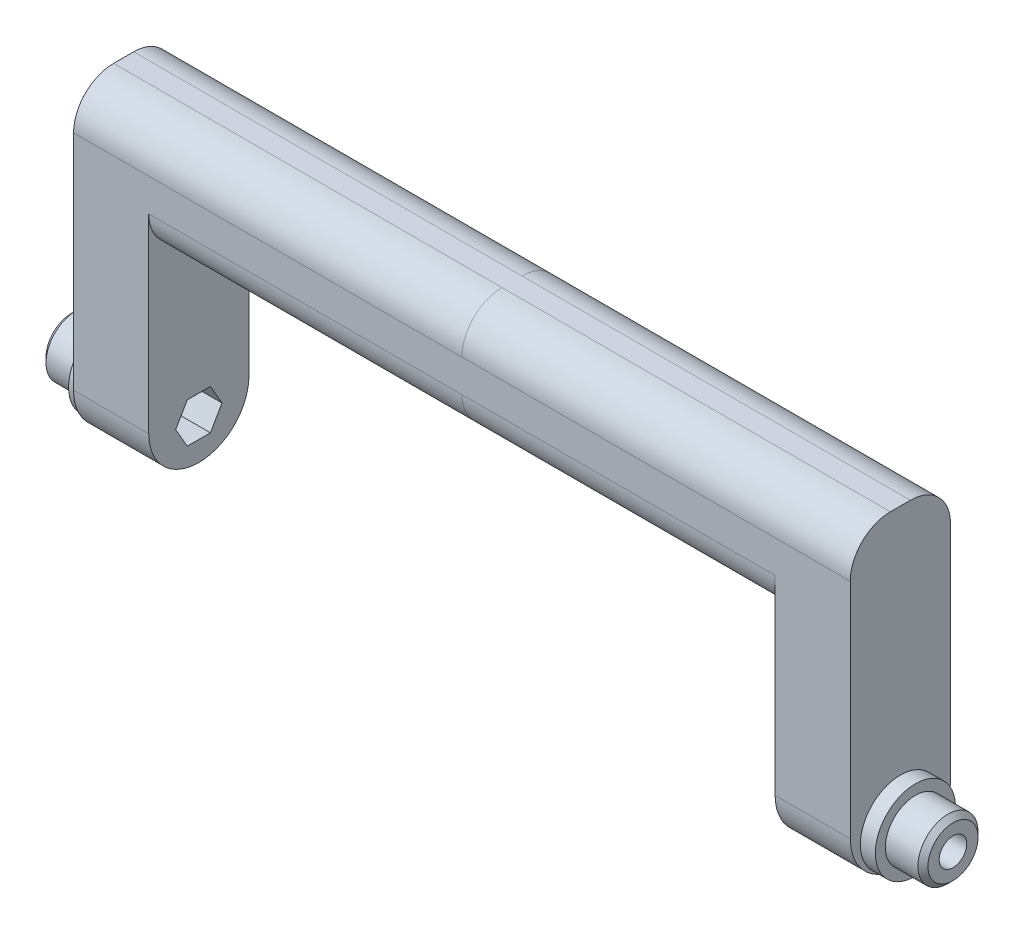
SolidWorks part; units mm, degrees
material "PET"
ref_plane "Front Plane" through (0, 0, 0) normal (0, 0, 1) x (1, 0, 0)
ref_plane "Top Plane" through (0, 0, 0) normal (0, 1, 0) x (1, 0, 0)
ref_plane "Right Plane" through (0, 0, 0) normal (1, 0, 0) x (0, 0, -1)
sketch "Sketch1" plane through (0, 0, 0) normal (0, 0, 1) x (1, 0, 0)
  line L0 (0, 0) -> (0, 8)
  line L1 (0, 8) -> (3, 8)
  line L2 (3, 8) -> (3, 6)
  line L3 (3, 6) -> (10.5, 6)
  line L4 (10.5, 6) -> (10.5, 0)
  line L6 (0, 0) -> (10.5, 0) construction
  line L7 (0, 0) -> (10.5, 0)
  point P3 (3, 7)
  dimension "D1" = 16
  dimension "D2" = 12
  dimension "D3" = 3
  dimension "D4" = 7.5
revolve "connector_body" add sketch "Sketch1" angle 360 about L6
chamfer "connector_mounting_chamfer" distance 1 angle 45 1 edges at (10.5, 0, 6)
sketch "Sketch2" plane through (0, 0, 0) normal (0, 0, 1) x (1, 0, 0)
  line L0 (0, -8) -> (0, 54.5)
  line L1 (0, 54.5) -> (-77.5, 54.5)
  line L2 (-77.5, 54.5) -> (-77.5, 32)
  line L3 (-77.5, 32) -> (-15, 32)
  line L4 (-15, 32) -> (-15, -8)
  line L5 (-15, -8) -> (0, -8)
  dimension "D1" = 62.5
  dimension "D2" = 15
  dimension "D3" = 22.5
  dimension "D4" = 40
extrude "handle_body" add sketch "Sketch2" along normal blind 10 and the other way blind 10
fillet "lower_handle_fillet" radius 10 2 edges at (-7.5, -8, -10) (-7.5, -8, 10)
fillet "upper_handle_fillet" radius 8 4 edges at (-38.75, 54.5, -10) (-38.75, 54.5, 10) (-46.25, 32, -10) (-46.25, 32, 10)
sketch "Sketch4" plane through (10.5, 0, 0) normal (1, 0, 0) x (0, 0, -1)
  point P0 (0, 0)
hole_wizard "mounting_screw_hole" positions "Sketch4" profile "Sketch5" hole size "M5" standard "DIN" end condition through all
sketch "Sketch5" plane through (10.5, 0, 0) normal (0, 1, 0) x (0, 0, -1)
  line L0 (0, 0) -> (0, 88)
  line L1 (0, 88) -> (2.75, 88)
  line L2 (2.75, 88) -> (2.75, 0)
  line L5 (2.75, 0) -> (0, 0)
  line L11 (0, -6.35) -> (0, 107.95) construction
  dimension "Thru Hole Dia." = 5.5
  dimension "Thru Hole Depth" = 88
sketch "Sketch6" plane through (-15, 0, 0) normal (-1, 0, 0) x (0, 0, 1)
  line L1 (4.6188, 0) -> (2.3094, 4)
  line L2 (2.3094, 4) -> (-2.3094, 4)
  line L3 (-2.3094, 4) -> (-4.6188, 0)
  line L4 (-4.6188, 0) -> (-2.3094, -4)
  line L5 (-2.3094, -4) -> (2.3094, -4)
  line L6 (2.3094, -4) -> (4.6188, 0)
  circle A0 centre (0, 0) radius 4 construction
  dimension "D1" = 8
extrude "nut_cutout" cut sketch "Sketch6" against normal blind 6
ref_plane "mirror_plane" through (-77.5, 0, 0) normal (1, 0, 0) x (0, 0, -1)
mirror "handle_mirror" about plane through (-77.5, 0, 0) normal (1, 0, 0) of "lower_handle_fillet", "handle_body", "upper_handle_fillet"
mirror "connector_mirror" about plane through (-77.5, 0, 0) normal (1, 0, 0) of "nut_cutout", "mounting_screw_hole", "connector_body", "connector_mounting_chamfer"
